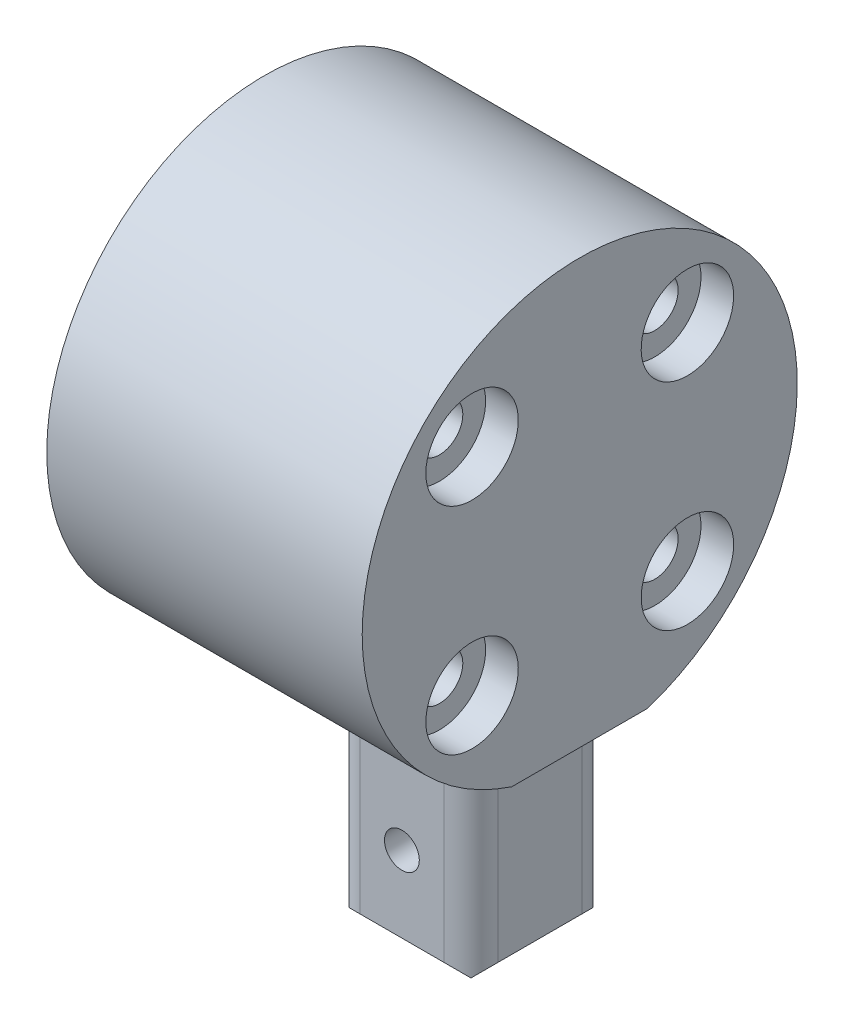
SolidWorks part; units mm, degrees
ref_plane "前视基准面" through (0, 0, 0) normal (0, 0, 1) x (1, 0, 0)
ref_plane "上视基准面" through (0, 0, 0) normal (0, 1, 0) x (1, 0, 0)
ref_plane "右视基准面" through (0, 0, 0) normal (1, 0, 0) x (0, 0, -1)
sketch "草图1" plane through (0, 0, 0) normal (1, 0, 0) x (0, 0, -1)
  circle A0 centre (0, 0) radius 20
  dimension "D1" = 40
extrude "凸台-拉伸1" add sketch "草图1" along normal blind 10
sketch "草图2" plane through (0, 0, 0) normal (-1, 0, 0) x (0, 0, 1)
  line L1 (-7.5, -15.25) -> (7.5, -15.25)
  line L2 (-7.5, -15.25) -> (-7.5, 15.25)
  line L3 (-7.5, 15.25) -> (7.5, 15.25)
  line L4 (7.5, -15.25) -> (7.5, 15.25)
  line L5 (-7.5, -15.25) -> (7.5, 15.25) construction
  line L6 (-7.5, 15.25) -> (7.5, -15.25) construction
  point P0 (0, 0)
  dimension "D1" = 15
  dimension "D2" = 30.5
extrude "切除-拉伸1" cut sketch "草图2" against normal blind 4
sketch "草图3" plane through (4, 0, 0) normal (-1, 0, 0) x (0, 0, 1)
  circle A0 centre (0, 0) radius 8.75
  dimension "D1" = 17.5
extrude "切除-拉伸2" cut sketch "草图3" along normal blind 4
sketch "草图4" plane through (0, 0, 0) normal (-1, 0, 0) x (0, 0, 1)
  line L1 (-9, -16) -> (9, -16)
  line L2 (-9, -16) -> (-9, 16)
  line L3 (-9, 16) -> (9, 16)
  line L4 (9, -16) -> (9, 16)
  line L5 (-9, -16) -> (9, 16) construction
  line L6 (-9, 16) -> (9, -16) construction
  circle A0 centre (0, 0) radius 20
  dimension "D3" = 40
  dimension "D1" = 32
  dimension "D2" = 18
extrude "凸台-拉伸2" add sketch "草图4" along normal blind 19
fillet "圆角1" radius 3 4 edges at (-9.5, -16, -9) (-9.5, -16, 9) (-9.5, 16, -9) (-9.5, 16, 9)
sketch "草图5" plane through (-19, 0, 0) normal (-1, 0, 0) x (0, 0, 1)
  line L0 (-6, -16) -> (6, -16) construction
  line L1 (6, 16) -> (-6, 16) construction
  circle A0 centre (0, -16) radius 2.5
  circle A1 centre (0, 16) radius 2.5
  dimension "D1" = 5
  dimension "D2" = 5
extrude "切除-拉伸3" cut sketch "草图5" against normal blind 20
fillet "圆角2" radius 3 4 edges at (-9.5, -16, -2.5) (-9.5, -16, 2.5) (-9.5, 16, -2.5) (-9.5, 16, 2.5)
sketch "草图6" plane through (10, 0, 0) normal (1, 0, 0) x (0, 0, -1)
  line L0 (0, 0) -> (20, 0) construction
  line L1 (0, 0) -> (18.216, -18.216) construction
  circle A0 centre (0, 0) radius 14 construction
  circle A2 centre (9.8995, -9.8995) radius 2.15
  circle A3 centre (0, 0) radius 14 construction
  circle A4 centre (-9.8995, -9.8995) radius 2.15
  circle A5 centre (0, 0) radius 14 construction
  circle A6 centre (-9.8995, 9.8995) radius 2.15
  circle A7 centre (0, 0) radius 14 construction
  circle A8 centre (9.8995, 9.8995) radius 2.15
  point P21 (0, 0)
  dimension "D1" = 28
  dimension "D3" = 4.3
  dimension "D2" = 45
  dimension "D4" = 4
extrude "切除-拉伸4" cut sketch "草图6" against normal blind 43
fillet "圆角3" radius 1 8 edges at (-9.5, -11.8523, 9) (-9.5, -7.9467, 9) (-9.5, -11.8523, -9) (-9.5, -7.9467, -9) (-9.5, 7.9467, -9) (-9.5, 11.8523, -9) (-9.5, 7.9467, 9) (-9.5, 11.8523, 9)
sketch "草图7" plane through (10, 0, 0) normal (1, 0, 0) x (0, 0, -1)
  circle A0 centre (9.8995, -9.8995) radius 4.25
  dimension "D1" = 8.5
extrude "切除-拉伸5" cut sketch "草图7" against normal blind 3
pattern_circular "阵列(圆周)1" count 4 over 360 about axis through (10, 0, 0) along (1, 0, 0) of "切除-拉伸5"
sketch "草图8" plane through (10, 0, 0) normal (1, 0, 0) x (0, 0, -1)
  line L1 (-11.4701, -19) -> (11.4701, -19)
  line L2 (-11.4701, -19) -> (-11.4701, -28.3124)
  line L3 (-11.4701, -28.3124) -> (11.4701, -28.3124)
  line L4 (11.4701, -19) -> (11.4701, -28.3124)
  line L5 (-11.4701, -19) -> (11.4701, -28.3124) construction
  line L6 (-11.4701, -28.3124) -> (11.4701, -19) construction
  point P0 (0, -23.6562)
  dimension "D1" = 19
extrude "切除-拉伸6" cut sketch "草图8" against normal blind 23
sketch "草图9" plane through (0, -19, 0) normal (0, -1, 0) x (1, 0, 0)
  line L1 (-3, -3) -> (3, -3)
  line L2 (-3, -3) -> (-3, 3)
  line L3 (-3, 3) -> (3, 3)
  line L4 (3, -3) -> (3, 3)
  line L5 (-3, -3) -> (3, 3) construction
  line L6 (-3, 3) -> (3, -3) construction
  point P0 (0, 0)
  dimension "D1" = 6
  dimension "D2" = 6
extrude "切除-拉伸7" cut sketch "草图9" against normal blind 4
sketch "草图10" plane through (0, -19, 0) normal (0, -1, 0) x (1, 0, 0)
  line L0 (10, -6.245) -> (10, 6.245) construction
  line L1 (-6.35, -6.35) -> (6.35, -6.35)
  line L2 (-6.35, -6.35) -> (-6.35, 6.35)
  line L3 (-6.35, 6.35) -> (6.35, 6.35)
  line L4 (6.35, -6.35) -> (6.35, 6.35)
  line L5 (-6.35, -6.35) -> (6.35, 6.35) construction
  line L6 (-6.35, 6.35) -> (6.35, -6.35) construction
  line L7 (-3, -3) -> (3, -3)
  line L8 (-3, -3) -> (-3, 3)
  line L9 (-3, 3) -> (3, 3)
  line L10 (3, -3) -> (3, 3)
  line L11 (-3, -3) -> (3, 3) construction
  line L12 (-3, 3) -> (3, -3) construction
  point P0 (0, 0)
  point P6 (0, 0)
  dimension "D1" = 12.7
  dimension "D2" = 12.7
  dimension "D3" = 10
extrude "凸台-拉伸3" add sketch "草图10" along normal blind 20 and the other way blind 0.5
sketch "草图11" plane through (-6.35, 0, 0) normal (-1, 0, 0) x (0, 0, 1)
  line L0 (-6.245, -19) -> (6.245, -19) construction
  line L1 (6.35, -18.9652) -> (6.35, -39) construction
  line L2 (-6.35, -18.9652) -> (-6.35, -39) construction
  circle A0 centre (0, -29) radius 1.6
  dimension "D1" = 3.2
  dimension "D2" = 10
  dimension "D3" = 6.35
  dimension "D4" = 6.35
extrude "切除-拉伸8" [suppressed] cut sketch "草图11" against normal blind 20
chamfer "倒角1" distance 3 angle 45 2 edges at (-3, -27.7342, -3) (-3, -27.7342, 3)
fillet "圆角4" radius 2 4 edges at (-0.5003, -16.8675, 2.4997) (-0.5003, -16.8675, -2.4997) (-1.8082, -18.1976, 1.1918) (-1.8082, -18.1976, -1.1918)
chamfer "倒角2" distance 3 angle 45 4 edges at (6.35, -39, 0) (0, -39, -6.35) (-6.35, -39, 0) (0, -39, 6.35)
sketch "草图13" plane through (0, -39, 0) normal (0, -1, 0) x (1, 0, 0)
  circle A0 centre (0, 0) radius 3.35
  dimension "D1" = 6.7
fillet "圆角5" radius 2.5 4 edges at (6.35, -27.4826, -6.35) (6.35, -27.4826, 6.35) (-6.35, -27.4826, 6.35) (-6.35, -27.4826, -6.35)
chamfer "倒角3" distance 1 angle 45 1 edges at (-13, -19, 0)
sketch "草图14" plane through (0, 0, -6.35) normal (0, 0, -1) x (-1, 0, 0)
  line L0 (-3.35, -39) -> (3.35, -39) construction
  line L1 (6.35, -19) -> (6.35, -36) construction
  circle A0 centre (0, -29) radius 1.6
  dimension "D1" = 3.2
  dimension "D2" = 10
  dimension "D3" = 6.35
extrude "切除-拉伸9" cut sketch "草图14" against normal through all both and the other way through all
